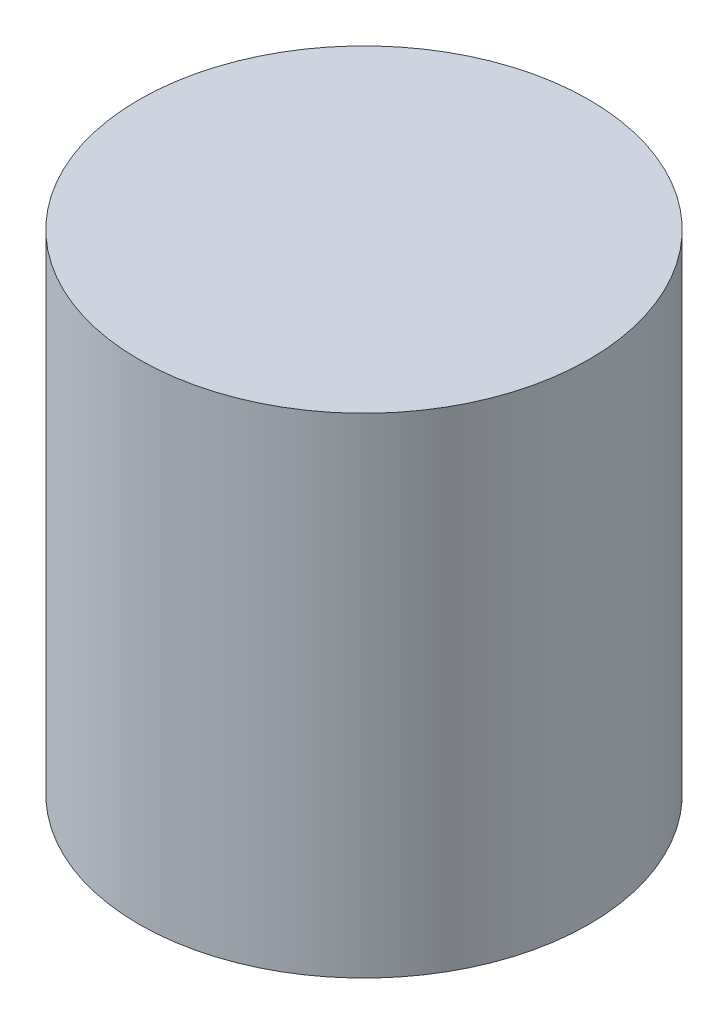
SolidWorks part; units mm, degrees
ref_plane "Front Plane" through (0, 0, 0) normal (0, 0, 1) x (1, 0, 0)
ref_plane "Top Plane" through (0, 0, 0) normal (0, 1, 0) x (1, 0, 0)
ref_plane "Right Plane" through (0, 0, 0) normal (1, 0, 0) x (0, 0, -1)
body saved out of another part "Stock-Base rib-1" rebuild error yes
sketch "Sketch1" plane through (0, 13.1889, 0) normal (0, 1, 0) x (1, 0, 0)
  line L0 (52.2211, 6.35) -> (179.2211, 6.35) construction
  line L1 (52.2211, 12.7) -> (52.2211, 0) construction
  line L2 (179.2211, 0) -> (179.2211, 12.7) construction
  circle A0 centre (77.6211, 6.35) radius 3.175
  circle A1 centre (153.8211, 6.35) radius 2.921
  dimension "D1" = 6.35
  dimension "D2" = 5.842
  dimension "D3" = 25.4
  dimension "D4" = 25.4
extrude "Boss-Extrude1" add sketch "Sketch1" along normal blind 6.35 contours A1 L0 | L0 A1 region at (153.8211, 13.1889, -7.5897) region at (153.8211, 13.1889, -5.1103)
extrude "Cut-Extrude1" cut sketch "Sketch1<3>" against normal blind 6.35 contours L0 A0 | A0 rebuild error yes
sketch "Sketch1<3>" plane through (0, 13.1889, 0) normal (0, 1, 0) x (1, 0, 0) same geometry as "Sketch1"
sketch "Sketch2" plane through (0, 0, 0) normal (0, 0, 1) x (1, 0, 0)
  line L0 (179.2211, 13.1889) -> (179.2211, 20.9808) construction
  line L1 (52.2211, 13.1889) -> (179.2211, 13.1889) construction
  circle A0 centre (128.4211, 8.7439) radius 2.54
  dimension "D1" = 5.08
  dimension "D2" = 50.8
  dimension "D3" = 4.445
extrude "Cut-Extrude2" cut sketch "Sketch2" against normal through all rebuild error yes
